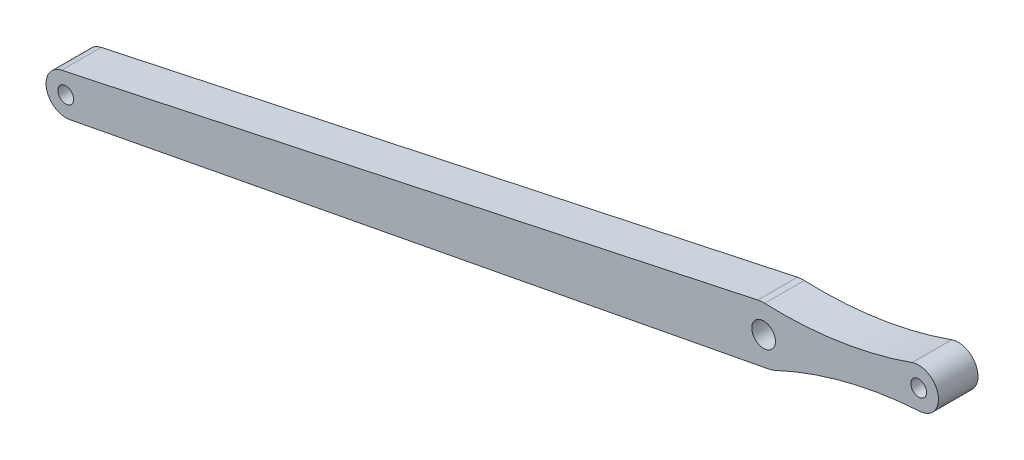
SolidWorks part; units mm, degrees
ref_plane "Front Plane" through (0, 0, 0) normal (0, 0, 1) x (1, 0, 0)
ref_plane "Top Plane" through (0, 0, 0) normal (0, 1, 0) x (1, 0, 0)
ref_plane "Right Plane" through (0, 0, 0) normal (1, 0, 0) x (0, 0, -1)
sketch "Sketch1" plane through (0, 0, 0) normal (0, 0, 1) x (1, 0, 0)
  line L0 (-51.8532, 154.8443) -> (-227.8537, 117.1637)
  line L3 (-49.0748, 141.1237) -> (-225.8691, 107.3632)
  circle A2 centre (-50.3878, 147.9994) radius 7
  circle A3 centre (-226.8069, 112.2745) radius 5
  circle A4 centre (-11.1835, 155.9383) radius 5
  arc A5 (-50.1155, 154.9941) -> (-12.8522, 160.6516) centre (-46.2254, 254.9184) ccw
  arc A6 (-10.887, 150.9471) -> (-47.4156, 141.6617) centre (-4.9568, 51.1231) ccw
  circle A7 centre (-226.8069, 112.2745) radius 2 construction
  circle A8 centre (-226.8069, 112.2745) radius 2
  circle A9 centre (-50.3878, 147.9994) radius 3 construction
  circle A10 centre (-50.3878, 147.9994) radius 3
  circle A11 centre (-11.1835, 155.9383) radius 2 construction
  circle A12 centre (-11.1835, 155.9383) radius 2
  dimension "D1" = 14
  dimension "D2" = 10
  dimension "D3" = 10
  dimension "D4" = 100
  dimension "D5" = 100
extrude "Boss-Extrude1" add sketch "Sketch1" along normal blind 5 and the other way blind 5 contours A3 L3 A2 L0 | A3 | A2 | A6 A4 A5 A2 | A4 region at (-134.9754, 130.8704, 0) region at (-50.972, 154.7763, 0) region at (-223.7521, 116.0526, 0) region at (-30.6388, 151.9986, 0) region at (-8.3792, 159.9059, 0)
